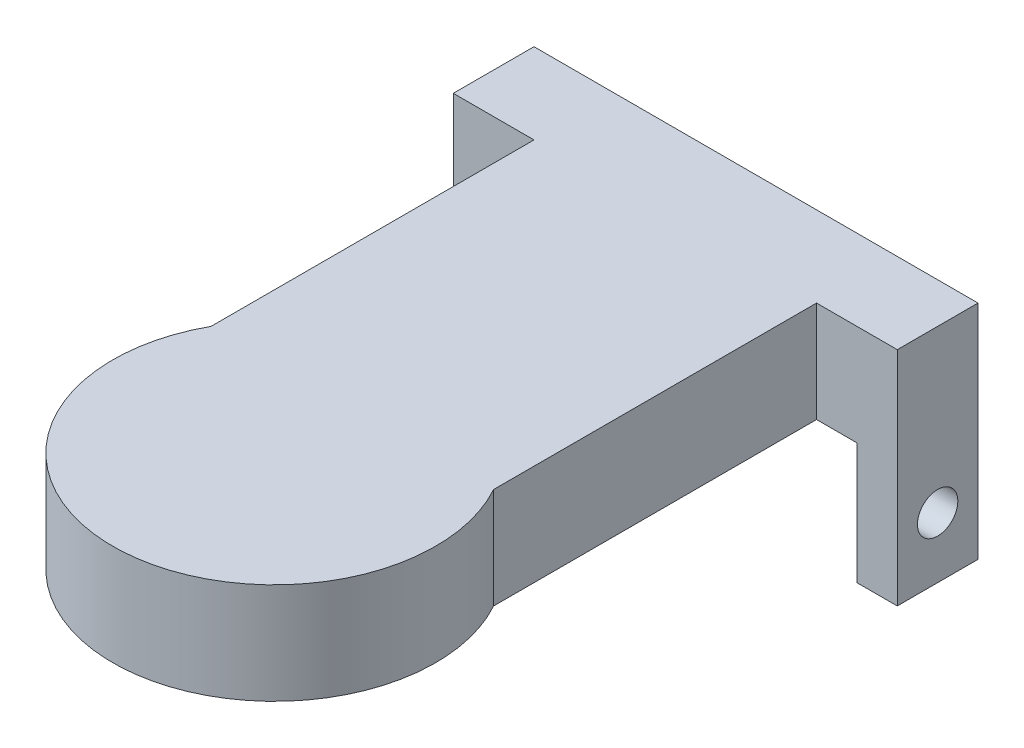
SolidWorks part; units mm, degrees
ref_plane "Front Plane" through (0, 0, 0) normal (0, 0, 1) x (1, 0, 0)
ref_plane "Top Plane" through (0, 0, 0) normal (0, 1, 0) x (1, 0, 0)
ref_plane "Right Plane" through (0, 0, 0) normal (1, 0, 0) x (0, 0, -1)
sketch "Sketch1" plane through (0, 0, 0) normal (0, 1, 0) x (1, 0, 0)
  circle A21 centre (0, 0) radius 20
  dimension "D1" = 40
extrude "Boss-Extrude1" add sketch "Sketch1" along normal blind 10
sketch "Sketch2" plane through (0, 10, 0) normal (0, 1, 0) x (1, 0, 0)
  line L5 (-3.6, 1.9621) -> (-3.6, -1.9621)
  line L6 (-1.9621, 3.6) -> (1.9621, 3.6)
  arc A3 (-3.6, -1.9621) -> (1.9621, 3.6) centre (0, 0) ccw
  arc A4 (-1.9621, 3.6) -> (-3.6, 1.9621) centre (0, 0) ccw
  point P0 (0, 0)
  point P1 (0, 0)
  point P18 (-3.6, 0)
  point P19 (0, 3.6)
  point P20 (0, 0)
  dimension "D4" = 4.1
  dimension "D5" = 3.9243
  dimension "D6" = 3.9243
extrude "Cut-Extrude1" cut sketch "Sketch2" against normal through all contours L6 A4 L5 A3 region at (0.1004, 10, 0.1004)
sketch "Sketch3" plane through (0, 0, 0) normal (0, 1, 0) x (1, 0, 0)
  line L0 (-17.5, 59.6825) -> (-17.5, 9.6825)
  line L1 (-17.5, 59.6825) -> (17.5, 59.6825)
  line L2 (17.5, 59.6825) -> (17.5, 9.6825)
  circle A0 centre (0, 0) radius 20 construction
  arc A1 (17.5, 9.6825) -> (-17.5, 9.6825) centre (0, 0) ccw
  point P6 (0, 59.6825)
  dimension "D1" = 35
  dimension "D2" = 50
extrude "Boss-Extrude2" add sketch "Sketch3" along normal up to surface (10 mm away) up to face at (0, 10, 20)
sketch "Sketch5" plane through (0, 0, 0) normal (0, -1, 0) x (1, 0, 0)
  line L3 (-1.9621, -3.6) -> (1.9621, -3.6) construction
  line L4 (-3.6, -1.9621) -> (-3.6, 1.9621) construction
  line L5 (-1.9621, -3.6) -> (1.9621, -3.6)
  line L6 (-3.6, -1.9621) -> (-3.6, 1.9621)
  circle A0 centre (0, 0) radius 12.5
  arc A2 (1.9621, -3.6) -> (-3.6, 1.9621) centre (0, 0) ccw construction
  arc A3 (-3.6, -1.9621) -> (-1.9621, -3.6) centre (0, 0) ccw construction
  arc A4 (1.9621, -3.6) -> (-3.6, 1.9621) centre (0, 0) ccw
  arc A5 (-3.6, -1.9621) -> (-1.9621, -3.6) centre (0, 0) ccw
  dimension "D1" = 25
extrude "Boss-Extrude3" add sketch "Sketch5" along normal blind 6
sketch "Sketch6" plane through (0, 0, -59.6825) normal (0, 0, -1) x (-1, 0, 0)
  line L0 (-27.5, 10) -> (27.5, 10)
  line L1 (-27.5, 10) -> (-27.5, -15)
  line L2 (-27.5, -15) -> (-22.5, -15)
  line L3 (-22.5, -15) -> (-22.5, 0)
  line L4 (-22.5, 0) -> (22.5, 0)
  line L5 (22.5, 0) -> (22.5, -15)
  line L6 (22.5, -15) -> (27.5, -15)
  line L7 (27.5, -15) -> (27.5, 10)
  line L8 (-17.5, 10) -> (17.5, 10) construction
  line L9 (-17.5, 0) -> (17.5, 0) construction
  point P10 (0, 0)
  dimension "D1" = 45
  dimension "D2" = 5
  dimension "D3" = 15
extrude "Boss-Extrude4" add sketch "Sketch6" against normal blind 10
sketch "Sketch7" plane through (27.5, 0, 0) normal (1, 0, 0) x (0, 0, -1)
  line L0 (49.6825, -15) -> (59.6825, -15) construction
  line L1 (9.6825, 0) -> (49.6825, 0) construction
  circle A0 centre (54.6825, -7.5) radius 2.5
  point P4 (54.6825, -15)
  dimension "D2" = 5
  dimension "D1" = 7.5
extrude "Cut-Extrude2" cut sketch "Sketch7" against normal through all
sketch "Sketch8" plane through (0, 10, 0) normal (0, 1, 0) x (1, 0, 0)
  line L0 (-27.5, 49.6825) -> (-27.5, 59.6825) construction
  line L1 (-27.5, 59.6825) -> (27.5, 59.6825)
  line L2 (-27.5, 59.6825) -> (-27.5, 49.6825)
  line L3 (-27.5, 49.6825) -> (-17.5, 49.6825)
  line L4 (27.5, 59.6825) -> (27.5, 49.6825)
  line L5 (27.5, 59.6825) -> (-27.5, 59.6825) construction
  line L6 (17.5, 49.6825) -> (27.5, 49.6825)
  line L8 (-17.5, 49.6825) -> (-17.5, 9.6825)
  line L10 (17.5, 49.6825) -> (17.5, 9.6825)
  arc A0 (-17.5, 9.6825) -> (17.5, 9.6825) centre (0, 0) ccw
extrude "Boss-Extrude5" add sketch "Sketch8" along normal blind 2.5
sketch "Sketch9" plane through (0, -6, 0) normal (0, -1, 0) x (1, 0, 0)
  circle A0 centre (0, 0) radius 12.5
  circle A1 centre (0, 0) radius 12.5 construction
extrude "Cut-Extrude3" cut sketch "Sketch9" against normal blind 2.5
